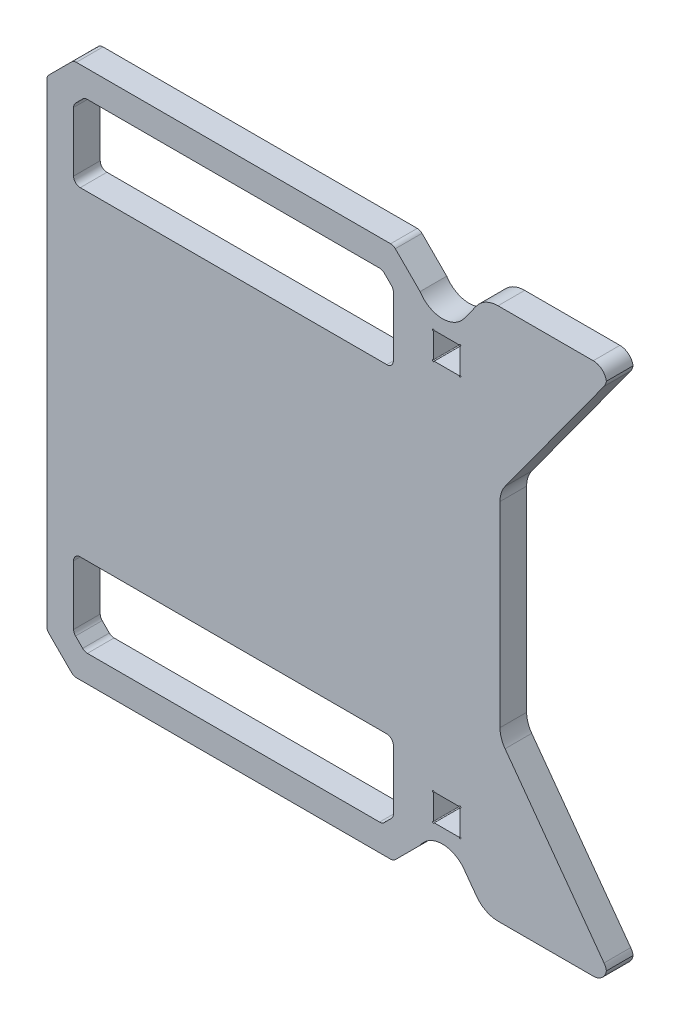
SolidWorks part; units mm, degrees
ref_plane "Front Plane" through (0, 0, 0) normal (0, 0, 1) x (1, 0, 0)
ref_plane "Top Plane" through (0, 0, 0) normal (0, 1, 0) x (1, 0, 0)
ref_plane "Right Plane" through (0, 0, 0) normal (1, 0, 0) x (0, 0, -1)
sketch "Sketch1" plane through (0, 0, 0) normal (0, 0, 1) x (1, 0, 0)
  line L0 (83.672, 0) -> (-43.8164, 0) construction
  line L1 (10.525, 38.1) -> (10.525, -38.1) construction
  line L2 (-27.575, 38.1) -> (48.625, 38.1)
  line L3 (99.425, -63.5) -> (99.425, -60.325)
  line L4 (99.425, -60.325) -> (74.025, -25.4)
  line L5 (-27.575, -63.5) -> (48.625, -63.5)
  line L6 (-27.575, 38.1) -> (-27.575, 54.5197)
  line L7 (48.625, 38.1) -> (48.625, 54.5197)
  line L8 (-24.9447, 57.15) -> (45.9947, 57.15)
  line L9 (-27.575, 63.5) -> (48.625, 63.5)
  line L10 (-33.925, 57.15) -> (-33.925, -57.15)
  line L11 (-27.575, 63.5) -> (-33.925, 57.15)
  line L12 (-24.9447, 57.15) -> (-27.575, 54.5197)
  line L13 (99.425, 63.5) -> (99.425, 60.325)
  line L14 (-23.0849, 59.0099) -> (-29.4349, 52.6599) construction
  line L15 (99.425, 60.325) -> (74.025, 25.4)
  line L16 (74.025, 25.4) -> (74.025, -25.4)
  line L17 (48.625, -38.1) -> (48.625, -54.5197)
  line L18 (-27.575, -38.1) -> (48.625, -38.1)
  line L19 (-24.9447, -57.15) -> (45.9947, -57.15)
  line L20 (-24.9447, -57.15) -> (-27.575, -54.5197)
  line L21 (-27.575, -38.1) -> (-27.575, -54.5197)
  line L22 (-27.575, -63.5) -> (-33.925, -57.15)
  line L23 (48.625, -63.5) -> (54.975, -57.15)
  line L24 (48.625, 63.5) -> (54.975, 57.15)
  line L25 (70.3271, -63.5) -> (99.425, -63.5)
  line L26 (45.9947, 57.15) -> (48.625, 54.5197)
  line L27 (45.9947, -57.15) -> (48.625, -54.5197)
  line L28 (70.3271, 63.5) -> (65.7089, 57.15)
  line L29 (70.3271, 63.5) -> (99.425, 63.5)
  line L30 (78.8831, 75.2646) -> (53.4831, 40.3396) construction
  line L31 (54.975, -42.3909) -> (54.975, -57.15)
  line L32 (70.3271, -63.5) -> (65.7089, -57.15)
  line L34 (48.625, -63.5) -> (54.975, -57.15)
  line L35 (65.7089, 57.15) -> (54.975, 42.3909)
  line L36 (54.975, 42.3909) -> (54.975, 57.15)
  line L37 (65.7089, -57.15) -> (54.975, -42.3909)
  point P7 (-27.575, 0)
  point P21 (74.025, 0)
  point P22 (-33.925, 0)
  dimension "D1" = 25.4
  dimension "D2" = 76.2
  dimension "D3" = 127
  dimension "D4" = 6.35
  dimension "D7" = 3.175
  dimension "D8" = 25.4
  dimension "D9" = 25.4
  dimension "D6" = 6.35
extrude "Boss-Extrude1" add sketch "Sketch1" along normal blind 6.35 contours L23 L32 L25 L3 L4 L16 L15 L13 L29 L28 L24 L9 L11 L10 L22 L5 L8 L26 L7 L2 L6 L12 L27 L19 L20 L21 L18 L17 region at (27.1557, 0, 0)
fillet "Fillet1" radius 6.35 4 edges at (70.3271, 63.5, 3.175) (70.3271, -63.5, 3.175) (54.975, -42.3909, 3.175) (54.975, 42.3909, 3.175)
fillet "Fillet3" radius 3.175 4 edges at (99.425, 63.5, 3.175) (99.425, 60.325, 3.175) (99.425, -60.325, 3.175) (99.425, -63.5, 3.175)
fillet "Fillet4" radius 6.35 2 edges at (74.025, -25.4, 3.175) (74.025, 25.4, 3.175)
fillet "Fillet7" radius 1.5875 4 edges at (-27.575, -38.1, 3.175) (48.625, -38.1, 3.175) (48.625, 38.1, 3.175) (-27.575, 38.1, 3.175)
fillet "Fillet8" radius 1.5875 6 edges at (-33.925, -57.15, 3.175) (-27.575, -63.5, 3.175) (48.625, -63.5, 3.175) (48.625, 63.5, 3.175) (-27.575, 63.5, 3.175) (-33.925, 57.15, 3.175)
fillet "Fillet9" radius 1.5875 8 edges at (-27.575, 54.5197, 3.175) (-24.9447, 57.15, 3.175) (-27.575, -54.5197, 3.175) (-24.9447, -57.15, 3.175) (45.9947, -57.15, 3.175) (48.625, -54.5197, 3.175) (48.625, 54.5197, 3.175) (45.9947, 57.15, 3.175)
sketch "Sketch2" plane through (0, 0, 6.35) normal (0, 0, 1) x (1, 0, 0)
  line L0 (-33.925, 0) -> (74.025, 0) construction
  line L1 (-33.925, 56.4924) -> (-33.925, -56.4924) construction
  line L2 (74.025, 23.3351) -> (74.025, -23.3351) construction
  line L3 (48.625, 39.6875) -> (48.625, 53.8622) construction
  line L4 (58.3484, 50.8) -> (64.3016, 50.8)
  line L5 (58.15, 50.6016) -> (58.15, 44.6484)
  line L6 (58.3484, 44.45) -> (64.3016, 44.45)
  line L7 (64.5, 50.6016) -> (64.5, 44.6484)
  line L8 (64.5, -50.6016) -> (64.5, -44.6484)
  line L9 (58.3484, -50.8) -> (64.3016, -50.8)
  line L10 (58.15, -50.6016) -> (58.15, -44.6484)
  line L11 (58.3484, -44.45) -> (64.3016, -44.45)
  arc A0 (58.3484, 50.8) -> (58.15, 50.6016) centre (58.15, 50.8) ccw
  arc A1 (64.5, 50.6016) -> (64.3016, 50.8) centre (64.5, 50.8) ccw
  arc A2 (64.3016, 44.45) -> (64.5, 44.6484) centre (64.5, 44.45) ccw
  arc A3 (58.15, 44.6484) -> (58.3484, 44.45) centre (58.15, 44.45) ccw
  arc A4 (64.3016, -44.45) -> (64.5, -44.6484) centre (64.5, -44.45) cw
  arc A5 (64.5, -50.6016) -> (64.3016, -50.8) centre (64.5, -50.8) cw
  arc A6 (58.3484, -50.8) -> (58.15, -50.6016) centre (58.15, -50.8) cw
  arc A7 (58.15, -44.6484) -> (58.3484, -44.45) centre (58.15, -44.45) cw
  point P10 (48.625, 46.7748)
  dimension "D5" = 0.3969
  dimension "D6" = 0.3969
  dimension "D7" = 0.3969
  dimension "D8" = 0.3969
  dimension "D1" = 6.35
  dimension "D2" = 6.35
  dimension "D3" = 50.8
  dimension "D4" = 9.525
extrude "Cut-Extrude1" cut sketch "Sketch2" against normal through all
